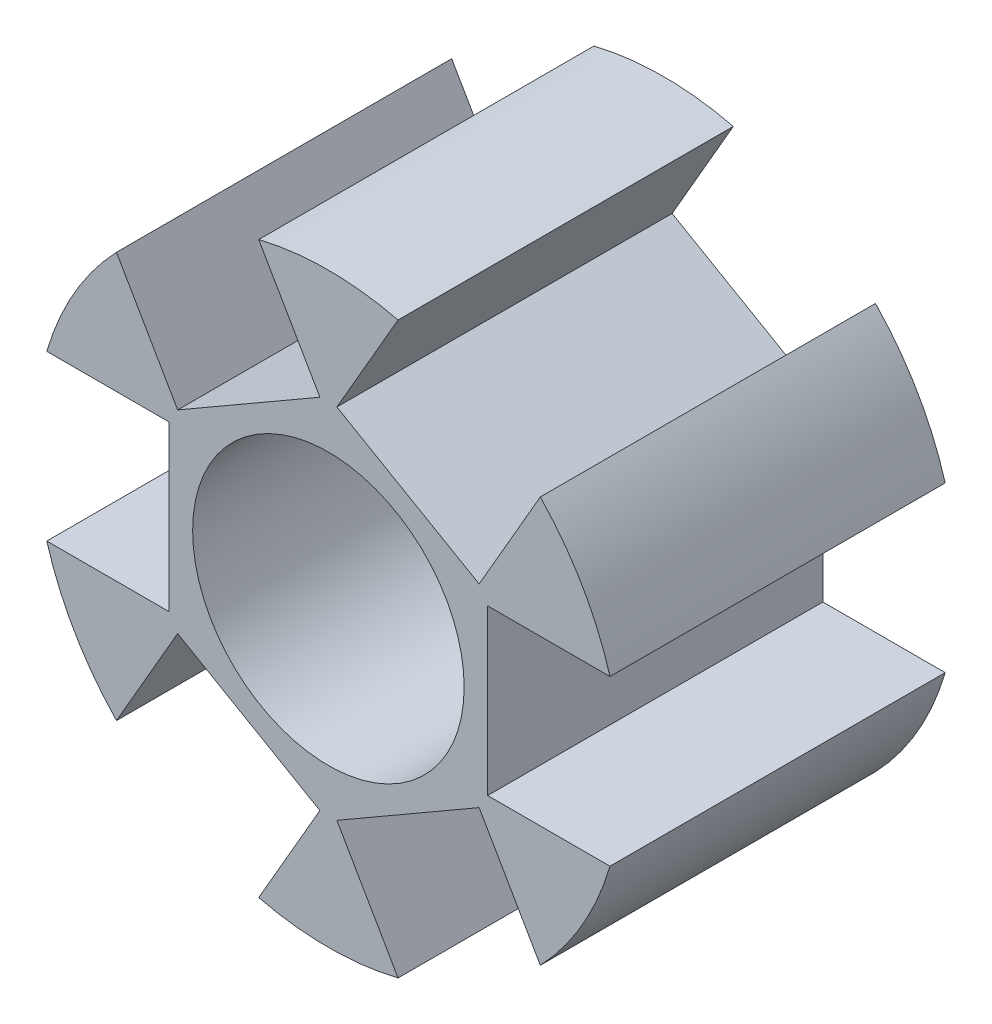
SolidWorks part; units mm, degrees
ref_plane "Top Plane" through (0, 0, 0) normal (0, 0, 1) x (1, 0, 0)
ref_plane "Right Plane" through (0, 0, 0) normal (0, 1, 0) x (1, 0, 0)
ref_plane "Front Plane" through (0, 0, 0) normal (1, 0, 0) x (0, 0, -1)
ref_axis "x-axis" through (-88.99, 0, 0) along (1, 0, 0)
ref_axis "y-axis" through (0, -55, 0) along (0, 1, 0)
ref_axis "z-axis" through (0, 0, 55) along (0, 0, -1)
sketch "Sketch1" plane through (0, 0, 0) normal (0, 0, 1) x (1, 0, 0)
  line L8 (-19.9785, 0) -> (0, 0) construction
  line L16 (0, 0) -> (0, -20.7846) construction
  line L23 (0, 0) -> (0, -20.7846) construction
  circle A0 centre (0, 0) radius 4.05
  circle A3 centre (0, 0) radius 8.75
  dimension "D1" = 8.1
  dimension "D2" = 17.5
extrude "Boss-Extrude1" add sketch "Sketch1" along normal mid plane 10
ref_plane "Plane1" through (-8.75, 0, 0) normal (-1, 0, 0) x (0, 0, 1)
sketch "Sketch2" plane through (-8.75, -17.1931, 0) normal (1, 0, 0) x (0, -1, 0)
  line L1 (-19.6431, -5) -> (-14.7431, -5)
  line L2 (-19.6431, -5) -> (-19.6431, 5)
  line L3 (-19.6431, 5) -> (-14.7431, 5)
  line L4 (-14.7431, -5) -> (-14.7431, 5)
  line L5 (-19.6431, -5) -> (-14.7431, 5) construction
  line L6 (-19.6431, 5) -> (-14.7431, -5) construction
  point P0 (-17.1931, 0)
  dimension "D1" = 4.9
  dimension "D2" = 10
extrude "Cut-Extrude3" cut sketch "Sketch2" along normal blind 4
pattern_circular "CirPattern1" count 6 over 360 about axis through (0, 0, 5) along (0, 0, 1) of "Cut-Extrude3"
